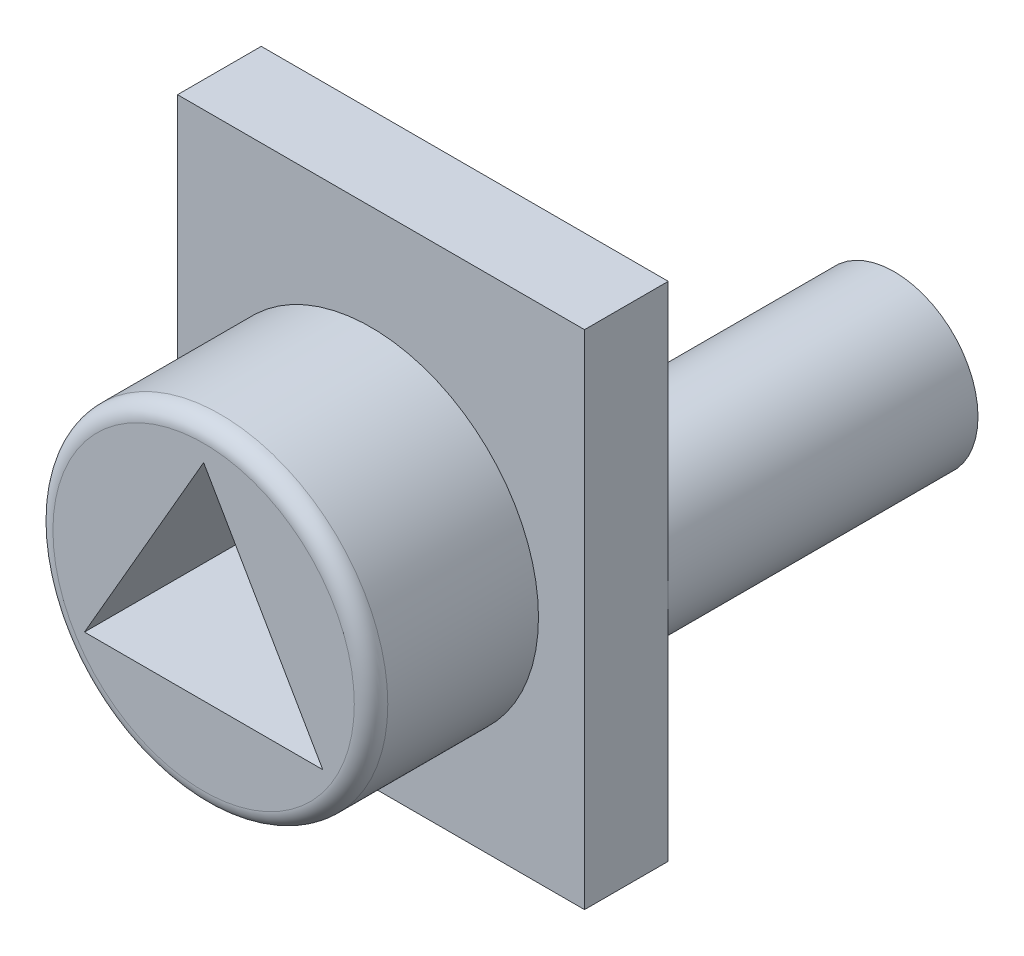
SolidWorks part; units mm, degrees
ref_plane "Спереди" through (0, 0, 0) normal (0, 0, 1) x (1, 0, 0)
ref_plane "Сверху" through (0, 0, 0) normal (0, 1, 0) x (1, 0, 0)
ref_plane "Справа" through (0, 0, 0) normal (1, 0, 0) x (0, 0, -1)
other "Configuration Table"
sketch "Эскиз1" plane through (0, 0, 0) normal (0, 0, 1) x (1, 0, 0)
  line L0 (-2.7384, -2.0301) -> (2.2616, -2.0301)
  line L1 (4.8616, -6) -> (4.8616, 6)
  line L2 (4.8616, 6) -> (-4.8616, 6)
  line L3 (-4.8616, 6) -> (-4.8616, -6)
  line L4 (-4.8616, -6) -> (4.8616, -6)
  line L5 (-0.2384, 2.3) -> (-2.7384, -2.0301)
  line L6 (2.2616, -2.0301) -> (-0.2384, 2.3)
  circle A0 centre (-0.2384, -0.5) radius 4
  circle A1 centre (2.8616, -0.5) radius 2
sketch "Эскиз2" plane through (0, 0, 0) normal (0, 0, 1) x (1, 0, 0)
  line L0 (-4.8616, -6) -> (4.8616, -6) construction
  line L1 (-4.8616, 6) -> (-4.8616, -6) construction
  line L2 (4.8616, 6) -> (-4.8616, 6) construction
  line L3 (4.8616, -6) -> (4.8616, 6) construction
  line L4 (-4.8616, -6) -> (4.8616, -6)
  line L5 (-4.8616, 6) -> (-4.8616, -6)
  line L6 (4.8616, 6) -> (-4.8616, 6)
  line L7 (4.8616, -6) -> (4.8616, 6)
extrude "Бобышка-Вытянуть1" add sketch "Эскиз2" along normal blind 2
sketch "Эскиз3" plane through (0, 0, 2) normal (0, 0, 1) x (1, 0, 0)
  line L6 (-3.0848, -2.2301) -> (-0.2384, 2.7)
  line L7 (-0.2384, 2.7) -> (2.608, -2.2301)
  line L8 (2.608, -2.2301) -> (-3.0848, -2.2301)
  line L9 (-0.2384, 2.3) -> (-2.7384, -2.0301) construction
  line L10 (2.2616, -2.0301) -> (-0.2384, 2.3) construction
  line L11 (-2.7384, -2.0301) -> (2.2616, -2.0301) construction
  circle A0 centre (-0.2384, -0.5) radius 4 construction
  circle A1 centre (-0.2384, -0.5) radius 4
  dimension "D1" = 0.2
  dimension "D2" = 0.2
  dimension "D3" = 0.2
extrude "Бобышка-Вытянуть2" add sketch "Эскиз3" along normal blind 4
sketch "Эскиз4" plane through (0, 0, 0) normal (0, 0, -1) x (-1, 0, 0)
  circle A0 centre (-2.8616, -0.5) radius 2 construction
  circle A1 centre (-2.8616, -0.5) radius 2
extrude "Бобышка-Вытянуть3" add sketch "Эскиз4" along normal blind 7.4
fillet "Скругление1" radius 0.4 1 edges at (3.7616, -0.5, 6)
sketch "hole" plane through (0, 0, 6) normal (0, 0, 1) x (1, 0, 0)
  line L0 (-3.0848, -2.2301) -> (2.608, -2.2301) construction
  line L1 (2.608, -2.2301) -> (-0.2384, 2.7) construction
  line L2 (-0.2384, 2.7) -> (-3.0848, -2.2301) construction
  line L3 (-3.0848, -2.2301) -> (2.608, -2.2301)
  line L4 (2.608, -2.2301) -> (-0.2384, 2.7)
  line L5 (-0.2384, 2.7) -> (-3.0848, -2.2301)
